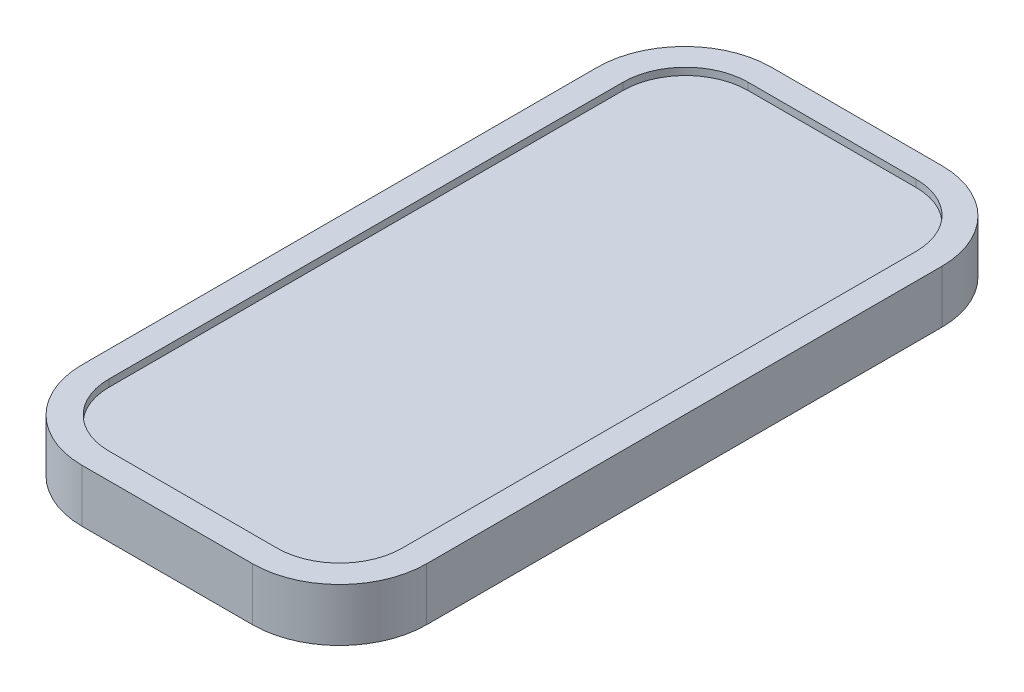
SolidWorks part; units mm, degrees
ref_plane "Front Plane" through (0, 0, 0) normal (0, 0, 1) x (1, 0, 0)
ref_plane "Top Plane" through (0, 0, 0) normal (0, 1, 0) x (1, 0, 0)
ref_plane "Right Plane" through (0, 0, 0) normal (1, 0, 0) x (0, 0, -1)
sketch "Sketch1" plane through (0, 0, 0) normal (0, 1, 0) x (1, 0, 0)
  line L1 (165.1, 0) -> (609.6, 0)
  line L2 (0, 165.1) -> (0, 1524)
  line L3 (165.1, 1689.1) -> (609.6, 1689.1)
  line L4 (774.7, 165.1) -> (774.7, 1524)
  arc A0 (0, 1524) -> (165.1, 1689.1) centre (165.1, 1524) cw
  arc A1 (774.7, 1524) -> (609.6, 1689.1) centre (609.6, 1524) ccw
  arc A2 (0, 165.1) -> (165.1, 0) centre (165.1, 165.1) ccw
  arc A3 (774.7, 165.1) -> (609.6, 0) centre (609.6, 165.1) cw
  point P7 (0, 1689.1)
  point P12 (0, 0)
  point P15 (774.7, 0)
  dimension "D3" = 165.1
  dimension "D4" = 165.1
  dimension "D5" = 165.1
  dimension "D6" = 165.1
  dimension "D1" = 774.7
  dimension "D2" = 1689.1
extrude "Boss-Extrude2" add sketch "Sketch1" against normal blind 10
sketch "Sketch2" plane through (0, 0, 0) normal (0, 1, 0) x (1, 0, 0)
  line L1 (165.1, 0) -> (609.6, 0)
  line L2 (0, 165.1) -> (0, 1524)
  line L3 (165.1, 1689.1) -> (609.6, 1689.1)
  line L4 (774.7, 165.1) -> (774.7, 1524)
  line L5 (162.1025, -68.0875) -> (612.5975, -68.0875)
  line L6 (-68.0875, 162.1025) -> (-68.0875, 1523.9975)
  line L7 (162.1025, 1754.1875) -> (612.5975, 1754.1875)
  line L8 (842.7875, 162.1025) -> (842.7875, 1523.9975)
  arc A0 (165.1, 1689.1) -> (0, 1524) centre (165.1, 1524) ccw
  arc A1 (609.6, 1689.1) -> (774.7, 1524) centre (609.6, 1524) cw
  arc A2 (774.7, 165.1) -> (609.6, 0) centre (609.6, 165.1) cw
  arc A3 (0, 165.1) -> (165.1, 0) centre (165.1, 165.1) ccw
  arc A4 (-68.0875, 162.1025) -> (162.1025, -68.0875) centre (162.1025, 162.1025) ccw
  arc A5 (842.7875, 162.1025) -> (612.5975, -68.0875) centre (612.5975, 162.1025) cw
  arc A6 (612.5975, 1754.1875) -> (842.7875, 1523.9975) centre (612.5975, 1523.9975) cw
  arc A7 (-68.0875, 1523.9975) -> (162.1025, 1754.1875) centre (162.1025, 1523.9975) cw
  point P14 (774.7, 1689.1)
  point P19 (0, 0)
  dimension "D5" = 165.1
  dimension "D6" = 165.1
  dimension "D7" = 165.1
  dimension "D8" = 165.1
  dimension "D9" = 230.19
  dimension "D10" = 230.19
  dimension "D11" = 230.19
  dimension "D12" = 230.19
  dimension "D1" = 65.0875
  dimension "D2" = 68.0875
  dimension "D3" = 68.0875
  dimension "D4" = 68.0875
extrude "Boss-Extrude3" add sketch "Sketch2" along normal blind 19.05 separate body
sketch "Sketch3" plane through (0, 0, 0) normal (0, -1, 0) x (1, 0, 0)
  line L0 (-68.0875, -1523.9975) -> (-68.0875, -162.1025) construction
  line L1 (162.1025, -1754.1875) -> (612.5975, -1754.1875)
  line L2 (-68.0875, -1523.9975) -> (-68.0875, -162.1025)
  line L3 (162.1025, 68.0875) -> (612.5975, 68.0875)
  line L4 (842.7875, -1523.9975) -> (842.7875, -162.1025)
  line L5 (612.5975, -1754.1875) -> (162.1025, -1754.1875) construction
  line L6 (842.7875, -162.1025) -> (842.7875, -1523.9975) construction
  line L7 (162.1025, 68.0875) -> (612.5975, 68.0875) construction
  line L8 (162.1025, -1734.1875) -> (612.5975, -1734.1875)
  line L9 (822.7875, -1523.9975) -> (822.7875, -162.1025)
  line L10 (162.1025, 48.0875) -> (612.5975, 48.0875)
  line L11 (-48.0875, -1523.9975) -> (-48.0875, -162.1025)
  arc A0 (-68.0875, -162.1025) -> (162.1025, 68.0875) centre (162.1025, -162.1025) cw
  arc A1 (842.7875, -162.1025) -> (612.5975, 68.0875) centre (612.5975, -162.1025) ccw
  arc A2 (612.5975, -1754.1875) -> (842.7875, -1523.9975) centre (612.5975, -1523.9975) ccw
  arc A3 (-68.0875, -1523.9975) -> (162.1025, -1754.1875) centre (162.1025, -1523.9975) ccw
  arc A4 (-48.0875, -1523.9975) -> (162.1025, -1734.1875) centre (162.1025, -1523.9975) ccw
  arc A5 (612.5975, -1734.1875) -> (822.7875, -1523.9975) centre (612.5975, -1523.9975) ccw
  arc A6 (822.7875, -162.1025) -> (612.5975, 48.0875) centre (612.5975, -162.1025) ccw
  arc A7 (-48.0875, -162.1025) -> (162.1025, 48.0875) centre (162.1025, -162.1025) cw
  dimension "D5" = 230.19
  dimension "D6" = 230.19
  dimension "D7" = 230.19
  dimension "D8" = 230.19
  dimension "D1" = 0
  dimension "D2" = 0
  dimension "D3" = 0
  dimension "D4" = 0
  dimension "D9" = 20
extrude "Boss-Extrude4" add sketch "Sketch3" along normal blind 120.65
sketch "Sketch4" plane through (0, 0, 0) normal (0, -1, 0) x (1, 0, 0)
  line L0 (612.5975, 48.0875) -> (162.1025, 48.0875) construction
  line L1 (241.3025, 48.0875) -> (533.4025, 48.0875)
  line L2 (241.3025, 48.0875) -> (241.3025, -2.7125)
  line L3 (241.3025, -2.7125) -> (533.4025, -2.7125)
  line L4 (533.4025, 48.0875) -> (533.4025, -2.7125)
  line L5 (-68.0875, -162.1025) -> (-68.0875, -1523.9975) construction
  line L8 (822.7875, -1523.9975) -> (822.7875, -162.1025) construction
  line L9 (822.7875, -256.7125) -> (-48.0875, -256.7125)
  line L10 (822.7875, -256.7125) -> (822.7875, -275.7625)
  line L11 (733.8875, -275.7625) -> (40.8125, -275.7625)
  line L12 (-48.0875, -256.7125) -> (-48.0875, -275.7625)
  line L13 (-48.0875, -162.1025) -> (-48.0875, -1523.9975) construction
  line L14 (822.7875, -224.9625) -> (558.8025, 48.0875)
  line L15 (612.5975, 48.0875) -> (162.1025, 48.0875) construction
  line L16 (215.9025, 48.0875) -> (-48.0875, -224.9625)
  line L17 (-48.0875, -162.1025) -> (-48.0875, -1523.9975) construction
  line L18 (198.2374, 48.0875) -> (-48.0875, -206.6912)
  line L20 (822.7875, -275.7625) -> (822.7875, -364.6625)
  line L21 (822.7875, -364.6625) -> (733.8875, -364.6625)
  line L22 (733.8875, -275.7625) -> (733.8875, -364.6625)
  line L24 (-48.0875, -275.7625) -> (-48.0875, -364.6625)
  line L25 (-48.0875, -364.6625) -> (40.8125, -364.6625)
  line L26 (40.8125, -275.7625) -> (40.8125, -364.6625)
  line L27 (822.7875, -206.691) -> (576.4674, 48.0875)
  line L28 (-48.0875, -224.9625) -> (-48.0875, -206.6912)
  line L29 (206.772, 56.915) -> (-57.218, -216.135) construction
  line L30 (215.9025, 48.0875) -> (198.2374, 48.0875)
  line L31 (822.7875, -224.9625) -> (822.7875, -206.691)
  line L32 (831.918, -216.1351) -> (567.933, 56.9149) construction
  line L33 (558.8025, 48.0875) -> (576.4674, 48.0875)
  dimension "D1" = 292.1
  dimension "D2" = 50.8
  dimension "D3" = 309.39
  dimension "D4" = 19.05
  dimension "D5" = 304.8
  dimension "D6" = 25.4
  dimension "D7" = 31.75
  dimension "D8" = 25.4
  dimension "D9" = 31.75
  dimension "D10" = 88.9
  dimension "D11" = 88.9
  dimension "D12" = 88.9
  dimension "D13" = 88.9
  dimension "D14" = 12.7
extrude "Boss-Extrude7" add sketch "Sketch4" along normal up to surface (120.65 mm away) from offset 5 separate body up to face at (387.35, -120.65, -843.05)
